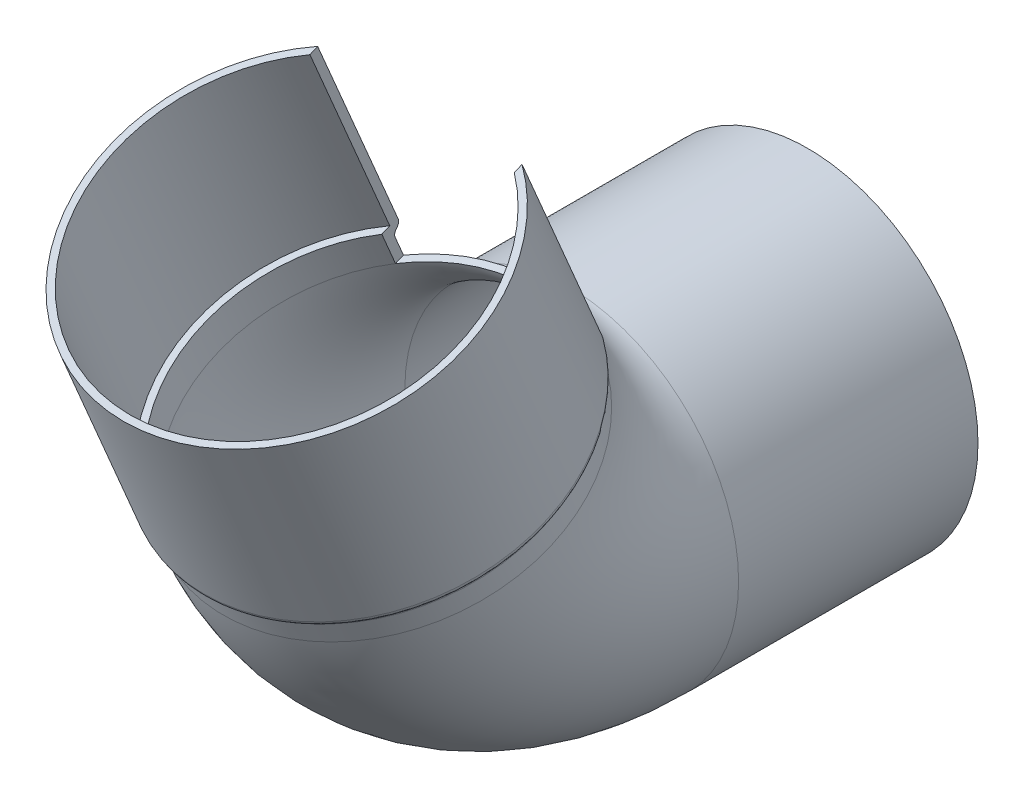
SolidWorks part; units mm, degrees
ref_plane "Plan de face" through (0, 0, 0) normal (0, 0, 1) x (1, 0, 0)
ref_plane "Plan de dessus" through (0, 0, 0) normal (0, 1, 0) x (1, 0, 0)
ref_plane "Plan de droite" through (0, 0, 0) normal (1, 0, 0) x (0, 0, -1)
sketch "Esquisse6" plane through (0, 0, 0) normal (0, 0, 1) x (1, 0, 0)
  circle A0 centre (0, 0) radius 25
sketch "Esquisse7" plane through (0, 0, 0) normal (1, 0, 0) x (0, 0, -1)
  line L0 (0, 0) -> (-35.1434, 0)
  line L1 (-62.7586, 18.2781) -> (-64.3775, 22.0921)
  arc A0 (-35.1434, 0) -> (-62.7586, 18.2781) centre (-35.1434, 30) cw
  point P6 (-55, 0)
  dimension "D4" = 30
  dimension "D1" = 24
  dimension "D2" = 55
  dimension "D3" = 67
sweep "Balayage-Mince2" add profiles "Esquisse6" path "Esquisse7" parameters "D1"=1
sketch "Esquisse8" plane through (0, 41.874, 17.7744) normal (0, 0.9205, 0.3907) x (1, 0, 0)
  line L0 (-24, -50.6278) -> (24, -50.6278) construction
  line L1 (0, -26.6278) -> (0, -74.6278) construction
  circle A0 centre (0, -50.6278) radius 24 construction
  circle A1 centre (0, -50.6278) radius 24 construction
  circle A2 centre (0, -50.6278) radius 24
  point P10 (0, -50.6278)
extrude "Extru.-Mince1" add sketch "Esquisse8" along normal blind 1 separate body thin contours A2
sketch "Esquisse9" plane through (0, 42.7945, 18.1652) normal (0, 0.9205, 0.3907) x (1, 0, 0)
  line L0 (-24, -50.6278) -> (24, -50.6278) construction
  line L1 (0, -26.6278) -> (0, -74.6278) construction
  circle A0 centre (0, -50.6278) radius 24 construction
  circle A1 centre (0, -50.6278) radius 24 construction
  circle A2 centre (0, -50.6278) radius 26
extrude "Extru.-Mince2" add sketch "Esquisse9" along normal blind 30 thin thin type one direction reverse wall 1
fillet "Congé1" radius 1 1 edges at (25, 22.0921, 64.3775)
fillet "Congé2" radius 1 1 edges at (26, 22.0921, 64.3775)
sketch "Esquisse10" plane through (0, 0, 0) normal (0, 0, 1) x (1, 0, 0)
  line L0 (-25, 0) -> (25, 0) construction
ref_plane "Plan1" through (0, 0, 0) normal (0, -0.3907, 0.9205) x (1, 0, 0)
sketch "Esquisse12" plane through (0, 0, 0) normal (0, -0.3907, 0.9205) x (1, 0, 0)
  line L0 (0, 76.4902) -> (0, 41.3468) construction
  line L1 (25, 76.4902) -> (-25, 76.4902) construction
  line L2 (25, 41.3468) -> (-25, 41.3468) construction
  line L4 (-15, 76.4902) -> (15, 76.4902)
  line L5 (-15, 76.4902) -> (-15, 41.3468)
  line L6 (-15, 41.3468) -> (15, 41.3468)
  line L7 (15, 76.4902) -> (15, 41.3468)
  dimension "D1" = 30
  dimension "D2" = 15
extrude "Enlèv. mat.-Extru.1" cut sketch "Esquisse12" along normal blind 40
